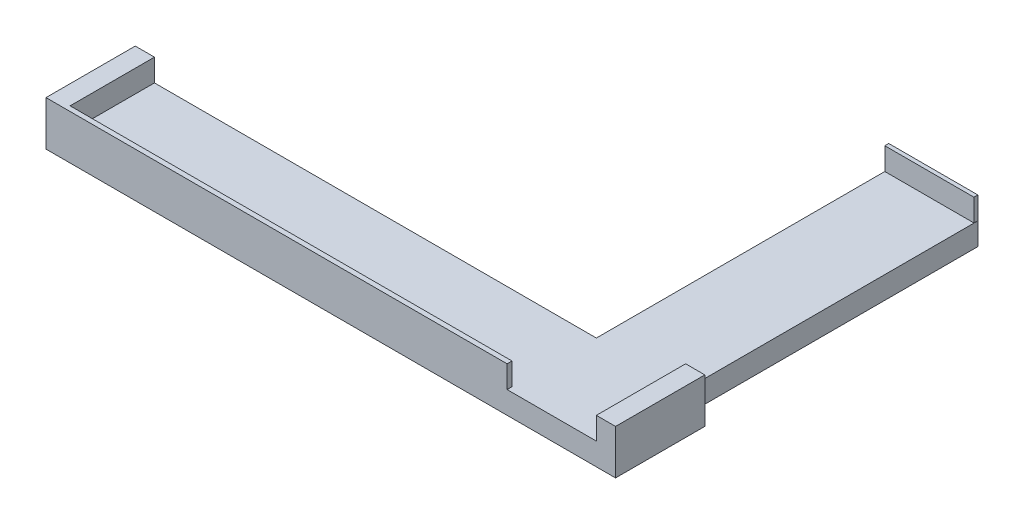
SolidWorks part; units mm, degrees
ref_plane "前视基准面" through (0, 0, 0) normal (0, 0, 1) x (1, 0, 0)
ref_plane "上视基准面" through (0, 0, 0) normal (0, 1, 0) x (1, 0, 0)
ref_plane "右视基准面" through (0, 0, 0) normal (1, 0, 0) x (0, 0, -1)
other "Configuration Table"
sketch "草图1" plane through (0, 0, 0) normal (0, 1, 0) x (1, 0, 0)
  line L1 (-63.8, -10) -> (63.8, -10)
  line L2 (-63.8, -10) -> (-63.8, 10)
  line L3 (-63.8, 10) -> (63.8, 10)
  line L4 (63.8, -10) -> (63.8, 10)
  line L5 (-63.8, -10) -> (63.8, 10) construction
  line L6 (-63.8, 10) -> (63.8, -10) construction
  line L7 (-63.8, 10) -> (-59.5, 10)
  line L8 (-63.8, 10) -> (-63.8, -10)
  line L9 (-63.8, -10) -> (-59.5, -10)
  line L10 (-59.5, 10) -> (-59.5, -10)
  line L11 (63.8, 10) -> (59.5, 10)
  line L12 (63.8, 10) -> (63.8, -10)
  line L13 (63.8, -10) -> (59.5, -10)
  line L14 (59.5, 10) -> (59.5, -10)
  line L15 (39.5, -10) -> (59.5, -10)
  line L16 (39.5, -10) -> (39.5, 75.5)
  line L17 (39.5, 75.5) -> (59.5, 75.5)
  line L18 (59.5, -10) -> (59.5, 75.5)
  line L19 (39.4687, 75.7204) -> (59.4687, 75.7204)
  line L20 (39.4687, 75.7204) -> (39.4687, 74.6204)
  line L21 (39.4687, 74.6204) -> (59.4687, 74.6204)
  line L22 (59.4687, 75.7204) -> (59.4687, 74.6204)
  line L27 (-59.5, -10) -> (39.5, -10)
  line L28 (-59.5, -10) -> (-59.5, -8.9002)
  line L29 (-59.5, -8.9002) -> (39.5, -8.9002)
  line L30 (39.5, -10) -> (39.5, -8.9002)
  point P0 (0, 0)
  dimension "D1" = 127.6
  dimension "D2" = 20
  dimension "D3" = 4.3
  dimension "D4" = 20
  dimension "D5" = 4.3
  dimension "D6" = 20
  dimension "D7" = 85.5
  dimension "D8" = 20
  dimension "D9" = 1.1
  dimension "D10" = 20
extrude "凸台-拉伸6" add sketch "草图1" along normal blind 10 contours L10 L3 L2 L1 | L29 L10 L1 L16 | L3 L14 L1 L4 | L22 L17 L16 L21 region at (-61.65, 0, 0) region at (-10, 0, 9.4501) region at (61.65, 0, 0) region at (49.4844, 0, -75.0602)
extrude "凸台-拉伸7" add sketch "草图1<15>" along normal blind 5 contours L10 L29 L16 L3 | L16 L1 L14 L3 | L17 L22 L21 L16 L3 L18 region at (49.5, 0, 0) region at (-10, 0, -0.5499) region at (49.5002, 0, -42.3109)
sketch "草图1<15>" plane through (0, 0, 0) normal (0, 1, 0) x (1, 0, 0) same geometry as "草图1"
